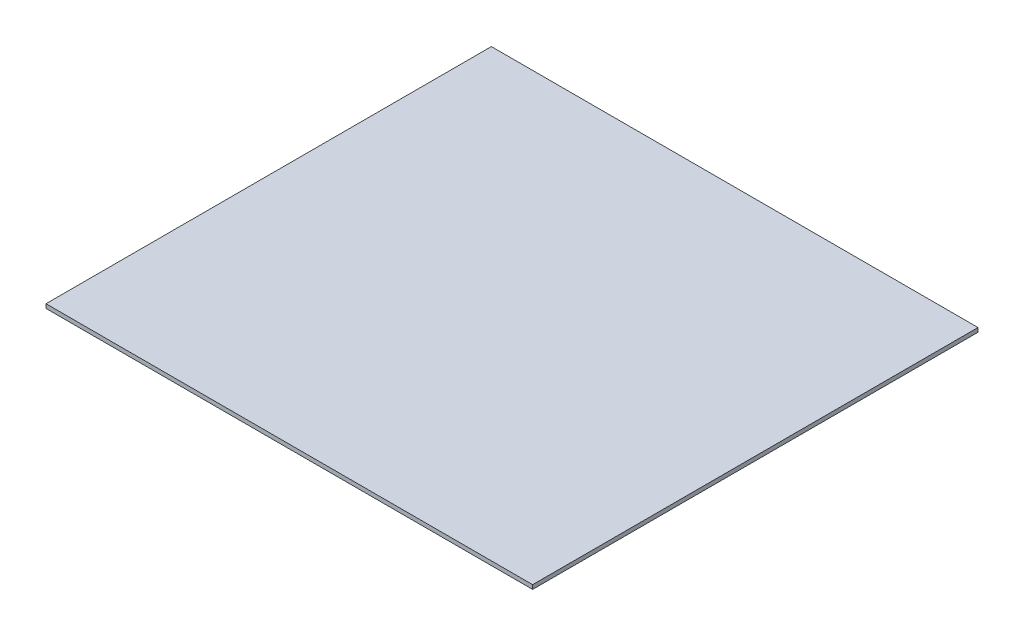
SolidWorks part; units mm, degrees
material "Acrylic (Medium-high impact)"
ref_plane "Front Plane" through (0, 0, 0) normal (0, 0, 1) x (1, 0, 0)
ref_plane "Top Plane" through (0, 0, 0) normal (0, 1, 0) x (1, 0, 0)
ref_plane "Right Plane" through (0, 0, 0) normal (1, 0, 0) x (0, 0, -1)
sketch "Sketch1" plane through (0, 0, 0) normal (0, 1, 0) x (1, 0, 0)
  line L1 (-187.325, -171.45) -> (187.325, -171.45)
  line L2 (-187.325, -171.45) -> (-187.325, 171.45)
  line L3 (-187.325, 171.45) -> (187.325, 171.45)
  line L4 (187.325, -171.45) -> (187.325, 171.45)
  line L5 (-187.325, -171.45) -> (187.325, 171.45) construction
  line L6 (-187.325, 171.45) -> (187.325, -171.45) construction
  point P0 (0, 0)
  dimension "D1" = 342.9
  dimension "D2" = 374.65
extrude "Boss-Extrude1" add sketch "Sketch1" along normal blind 3.175
